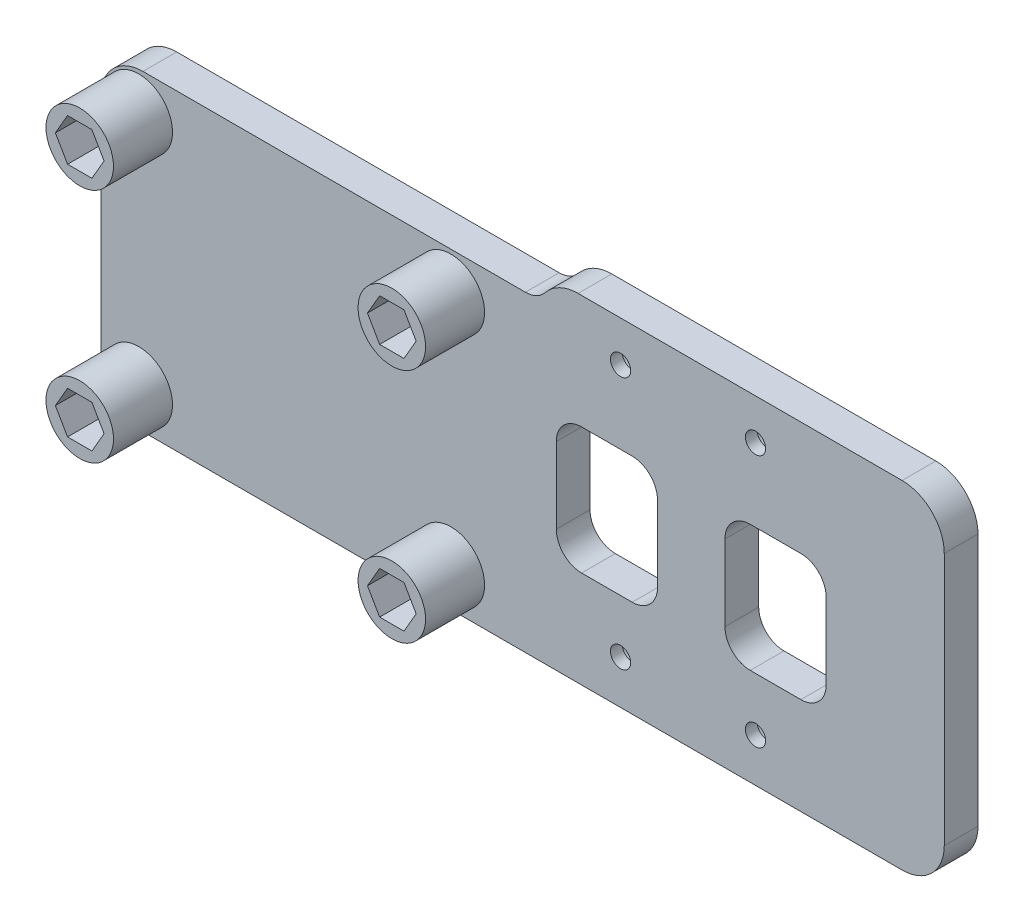
SolidWorks part; units mm, degrees
ref_plane "Front Plane" through (0, 0, 0) normal (0, 0, 1) x (1, 0, 0)
ref_plane "Top Plane" through (0, 0, 0) normal (0, 1, 0) x (1, 0, 0)
ref_plane "Right Plane" through (0, 0, 0) normal (1, 0, 0) x (0, 0, -1)
ref_plane "Plane1" through (0, 0, 34.8116) normal (0, 0, -1) x (-1, 0, 0)
sketch "Sketch1" plane through (0, 0, 34.8116) normal (0, 0, -1) x (-1, 0, 0)
  line L0 (-23.5355, 118.8347) -> (-23.5355, 78.8347)
  line L1 (-23.5355, 78.8347) -> (26.4645, 78.8347)
  line L2 (26.4645, 78.8347) -> (26.4645, 118.8347)
  line L3 (26.4645, 118.8347) -> (-23.5355, 118.8347)
extrude "Boss-Extrude1" add sketch "Sketch1" against normal blind 4
sketch "Sketch2" plane through (0, 0, 38.8116) normal (0, 0, 1) x (1, 0, 0)
  line L0 (23.5355, 90.3347) -> (23.5355, 105.3347)
  line L1 (23.5355, 105.3347) -> (15.5355, 105.3347)
  line L2 (15.5355, 105.3347) -> (15.5355, 90.3347)
  line L3 (15.5355, 90.3347) -> (23.5355, 90.3347)
  line L4 (23.5355, 118.8347) -> (23.5355, 78.8347) construction
  line L6 (15.5355, 105.3347) -> (23.5355, 90.3347) construction
  line L7 (15.5355, 90.3347) -> (23.5355, 105.3347) construction
  line L8 (23.5355, 78.8347) -> (-26.4645, 78.8347) construction
  point P6 (19.5355, 97.8347)
  dimension "D1" = 8
  dimension "D2" = 15
  dimension "D3" = 19
extrude "Cut-Extrude1" cut sketch "Sketch2" against normal through all
sketch "Sketch3" plane through (0, 0, 38.8116) normal (0, 0, 1) x (1, 0, 0)
  line L0 (7.5355, 105.3347) -> (-4.4645, 105.3347)
  line L1 (-4.4645, 105.3347) -> (-4.4645, 90.3347)
  line L2 (-4.4645, 90.3347) -> (7.5355, 90.3347)
  line L3 (7.5355, 90.3347) -> (7.5355, 105.3347)
  line L4 (23.5355, 105.3347) -> (15.5355, 105.3347) construction
  line L5 (15.5355, 90.3347) -> (23.5355, 90.3347) construction
  line L6 (15.5355, 105.3347) -> (15.5355, 90.3347) construction
  dimension "D1" = 8
  dimension "D2" = 12
extrude "Cut-Extrude2" cut sketch "Sketch3" against normal through all
hole_wizard "CBORE for M2 Pan Head Machine Screw1" positions "Sketch5" profile "Sketch4" counterbore size "M2" standard "ANSI Metric" end condition up to next
sketch "Sketch5" plane through (0, 0, 34.8116) normal (0, 0, -1) x (-1, 0, 0)
  point P0 (-3.1566, 84.0163)
  point P1 (-19.1566, 84.0163)
  point P2 (-19.1566, 114.0163)
  point P3 (-3.1566, 114.0163)
sketch "Sketch4" plane through (3.1566, 84.0163, 34.8116) normal (1, 0, 0) x (0, 1, 0)
  line L0 (0, 0) -> (0, 4)
  line L1 (0, 4) -> (1.2, 4)
  line L3 (1.2, 4) -> (1.2, 2.6)
  line L4 (1.2, 2.6) -> (2.5, 2.6)
  line L5 (2.5, 2.6) -> (2.5, 0)
  line L7 (2.5, 0) -> (0, 0)
  line L11 (0, -6.35) -> (0, 107.95) construction
  dimension "Thru Hole Dia." = 2.4
  dimension "Thru Hole Depth" = 4
  dimension "C'Bore Dia." = 5
  dimension "C'Bore Depth" = 2.6
sketch "Sketch6" plane through (0, 0, 38.8116) normal (0, 0, 1) x (1, 0, 0)
  line L0 (-26.4645, 78.8347) -> (-26.4645, 118.8347) construction
  line L1 (-11.4645, 78.8347) -> (-58.4645, 78.8347)
  line L2 (-11.4645, 78.8347) -> (-11.4645, 115.8347)
  line L3 (-11.4645, 115.8347) -> (-58.4645, 115.8347)
  line L4 (-58.4645, 78.8347) -> (-58.4645, 115.8347)
  line L7 (23.5355, 78.8347) -> (-26.4645, 78.8347) construction
  dimension "D1" = 47
  dimension "D2" = 37
  dimension "D3" = 15
extrude "Boss-Extrude2" add sketch "Sketch6" against normal up to surface (4 mm away) up to face at (0.6566, 84.0163, 34.8116)
sketch "Sketch7" plane through (0, 0, 38.8116) normal (0, 0, 1) x (1, 0, 0)
  line L0 (-53.9645, 111.3347) -> (-53.9645, 83.3347) construction
  line L1 (-58.4645, 97.3347) -> (-53.9645, 97.3347) construction
  line L2 (-58.4645, 115.8347) -> (-58.4645, 78.8347) construction
  line L4 (-11.4645, 78.8347) -> (-11.4645, 115.8347) construction
  circle A0 centre (-53.9645, 111.3347) radius 4
  circle A1 centre (-16.9645, 111.3347) radius 4
  circle A2 centre (-53.9645, 83.3347) radius 4
  circle A3 centre (-16.9645, 83.3347) radius 4
  dimension "D3" = 8
  dimension "D1" = 37
  dimension "D2" = 28
  dimension "D4" = 5.5
extrude "Boss-Extrude3" add sketch "Sketch7" along normal blind 7
hole_wizard "Ø2.7 (2.7) Diameter Hole1" positions "Sketch8" profile "Sketch9" hole size "Ø2.7" standard "ANSI Metric"
sketch "Sketch8" plane through (0, 0, 45.8116) normal (0, 0, 1) x (1, 0, 0)
  point P0 (-53.9645, 111.3347)
  point P3 (-16.9645, 111.3347)
  point P6 (-16.9645, 83.3347)
  point P9 (-53.9645, 83.3347)
sketch "Sketch9" plane through (-53.9645, 111.3347, 45.8116) normal (1, 0, 0) x (0, -1, 0)
  line L0 (0, 0) -> (0, 4.8112)
  line L1 (0, 4.8112) -> (1.35, 4)
  line L2 (1.35, 4) -> (1.35, 0)
  line L5 (1.35, 0) -> (0, 0)
  line L10 (0, 4.8112) -> (-1.35, 4) construction
  line L11 (0, -6.35) -> (0, 107.95) construction
  dimension "Hole Dia." = 2.7
  dimension "Hole Depth" = 4
  dimension "Drill Angle" = 118
sketch "Sketch10" plane through (0, 0, 45.8116) normal (0, 0, 1) x (1, 0, 0)
  line L0 (-26.4645, 115.8347) -> (-58.4645, 115.8347) construction
  line L1 (-52.5211, 113.8347) -> (-55.4078, 113.8347)
  line L2 (-55.4078, 113.8347) -> (-56.8512, 111.3347)
  line L3 (-56.8512, 111.3347) -> (-55.4078, 108.8347)
  line L4 (-55.4078, 108.8347) -> (-52.5211, 108.8347)
  line L5 (-52.5211, 108.8347) -> (-51.0777, 111.3347)
  line L6 (-51.0777, 111.3347) -> (-52.5211, 113.8347)
  line L8 (-52.5211, 85.8347) -> (-55.4078, 85.8347)
  line L9 (-55.4078, 85.8347) -> (-56.8512, 83.3347)
  line L10 (-56.8512, 83.3347) -> (-55.4078, 80.8347)
  line L11 (-55.4078, 80.8347) -> (-52.5211, 80.8347)
  line L12 (-52.5211, 80.8347) -> (-51.0777, 83.3347)
  line L13 (-51.0777, 83.3347) -> (-52.5211, 85.8347)
  line L14 (-15.5211, 113.8347) -> (-18.4078, 113.8347)
  line L15 (-18.4078, 113.8347) -> (-19.8512, 111.3347)
  line L16 (-19.8512, 111.3347) -> (-18.4078, 108.8347)
  line L17 (-18.4078, 108.8347) -> (-15.5211, 108.8347)
  line L18 (-15.5211, 108.8347) -> (-14.0777, 111.3347)
  line L19 (-14.0777, 111.3347) -> (-15.5211, 113.8347)
  line L20 (-15.5211, 85.8347) -> (-18.4078, 85.8347)
  line L21 (-18.4078, 85.8347) -> (-19.8512, 83.3347)
  line L22 (-19.8512, 83.3347) -> (-18.4078, 80.8347)
  line L23 (-18.4078, 80.8347) -> (-15.5211, 80.8347)
  line L24 (-15.5211, 80.8347) -> (-14.0777, 83.3347)
  line L25 (-14.0777, 83.3347) -> (-15.5211, 85.8347)
  circle A0 centre (-53.9645, 111.3347) radius 2.5 construction
  circle A1 centre (-53.9645, 83.3347) radius 2.5 construction
  circle A2 centre (-16.9645, 111.3347) radius 2.5 construction
  circle A3 centre (-16.9645, 83.3347) radius 2.5 construction
  dimension "D1" = 5
extrude "Cut-Extrude3" cut sketch "Sketch10" against normal blind 6.5
sketch "Sketch11" plane through (0, 0, 38.8116) normal (0, 0, 1) x (1, 0, 0)
  line L0 (23.5355, 118.8347) -> (41.5355, 118.8347)
  line L1 (41.5355, 118.8347) -> (41.5355, 78.8347)
  line L2 (41.5355, 78.8347) -> (23.5355, 78.8347)
  line L3 (23.5355, 78.8347) -> (23.5355, 90.3347)
  line L4 (23.5355, 90.3347) -> (23.5355, 78.8347) construction
  line L5 (23.5355, 90.3347) -> (27.5355, 90.3347)
  line L6 (27.5355, 90.3347) -> (27.5355, 105.3347)
  line L7 (27.5355, 105.3347) -> (23.5355, 105.3347)
  line L8 (23.5355, 105.3347) -> (23.5355, 118.8347)
  line L9 (23.5355, 78.8347) -> (-58.4645, 78.8347) construction
  line L10 (23.5355, 105.3347) -> (15.5355, 105.3347) construction
  line L11 (15.5355, 90.3347) -> (23.5355, 90.3347) construction
  line L12 (15.5355, 105.3347) -> (15.5355, 90.3347) construction
  line L13 (-58.4645, 115.8347) -> (-58.4645, 78.8347) construction
  dimension "D1" = 12
  dimension "D2" = 100
extrude "Boss-Extrude4" add sketch "Sketch11" against normal up to surface (4 mm away) up to face at (-4.4645, 101.8347, 34.8116)
sketch "Sketch12" plane through (0, 0, 38.8116) normal (0, 0, 1) x (1, 0, 0)
  line L0 (-26.4645, 115.8347) -> (-6.4645, 115.8347)
  line L1 (-6.4645, 115.8347) -> (-6.4645, 118.8347)
  line L2 (-26.4645, 118.8347) -> (41.5355, 118.8347) construction
  line L3 (-6.4645, 118.8347) -> (-26.4645, 118.8347)
  line L4 (-26.4645, 118.8347) -> (-26.4645, 115.8347)
  dimension "D1" = 20
extrude "Cut-Extrude4" cut sketch "Sketch12" against normal blind 10
sketch "Sketch13" plane through (0, 0, 34.8116) normal (0, 0, 1) x (1, 0, 0)
  line L3 (41.5355, 78.8347) -> (41.5355, 118.8347) construction
  line L4 (36.5355, 110.8347) -> (-53.4645, 110.8347) construction
  line L5 (36.5355, 110.8347) -> (36.5355, 83.8347) construction
  line L6 (36.5355, 83.8347) -> (-53.4645, 83.8347) construction
  line L7 (-53.4645, 110.8347) -> (-53.4645, 83.8347) construction
  line L8 (41.5355, 78.8347) -> (-58.4645, 78.8347) construction
  line L9 (-58.4645, 115.8347) -> (-58.4645, 78.8347) construction
  line L10 (-58.4645, 97.3347) -> (-53.4645, 97.3347) construction
  line L11 (-8.4645, 78.8347) -> (-8.4645, 83.8347) construction
  line L12 (36.5355, 110.8347) -> (-53.4645, 83.8347) construction
  line L13 (36.5355, 83.8347) -> (-53.4645, 110.8347) construction
  circle A4 centre (36.5355, 110.8347) radius 2.6
  circle A5 centre (36.5355, 83.8347) radius 2.6
  circle A6 centre (-53.4645, 110.8347) radius 2.6
  circle A7 centre (-53.4645, 83.8347) radius 2.6
  circle A8 centre (-8.4645, 97.3347) radius 2.6
  dimension "D1" = 5
  dimension "D2" = 5
  dimension "D3" = 5.2
extrude "Cut-Extrude5" cut sketch "Sketch13" along normal blind 2.2
sketch "Sketch14" plane through (0, 0, 34.8116) normal (0, 0, -1) x (-1, 0, 0)
  line L0 (-41.5355, 78.8347) -> (-41.5355, 118.8347) construction
  line L1 (-41.5355, 105.8347) -> (-31.5355, 105.8347)
  line L2 (-41.5355, 105.8347) -> (-41.5355, 115.8347) construction
  line L3 (-41.5355, 115.8347) -> (-31.5355, 115.8347)
  line L4 (-31.5355, 105.8347) -> (-31.5355, 115.8347)
  line L5 (-41.5355, 105.8347) -> (-31.5355, 115.8347) construction
  line L6 (-41.5355, 115.8347) -> (-31.5355, 105.8347) construction
  line L7 (-41.5355, 115.8347) -> (-41.5355, 118.8347)
  line L8 (6.4645, 118.8347) -> (-41.5355, 118.8347) construction
  line L9 (-41.5355, 118.8347) -> (6.4645, 118.8347)
  line L10 (6.4645, 118.8347) -> (6.4645, 115.8347)
  line L11 (6.4645, 115.8347) -> (58.4645, 115.8347)
  line L12 (58.4645, 115.8347) -> (58.4645, 78.8347)
  line L13 (58.4645, 78.8347) -> (-41.5355, 78.8347)
  line L14 (-41.5355, 78.8347) -> (-41.5355, 105.8347)
  circle A0 centre (-36.5355, 110.8347) radius 2.6 construction
  point P0 (-36.5355, 110.8347)
extrude "Cut-Extrude6" [suppressed] cut sketch "Sketch14" against normal up to next
fillet "Fillet1" radius 5 5 edges at (-58.4645, 115.8347, 36.8116) (-58.4645, 78.8347, 36.8116) (41.5355, 78.8347, 36.8116) (41.5355, 118.8347, 36.8116) (-6.4645, 118.8347, 36.8116)
fillet "Fillet2" radius 3 8 edges at (7.5355, 90.3347, 36.8116) (-4.4645, 90.3347, 36.8116) (15.5355, 90.3347, 36.8116) (27.5355, 90.3347, 36.8116) (15.5355, 105.3347, 36.8116) (7.5355, 105.3347, 36.8116) (-4.4645, 105.3347, 36.8116) (27.5355, 105.3347, 36.8116)
fillet "Fillet3" radius 3 1 edges at (-6.4645, 115.8347, 36.8116)
